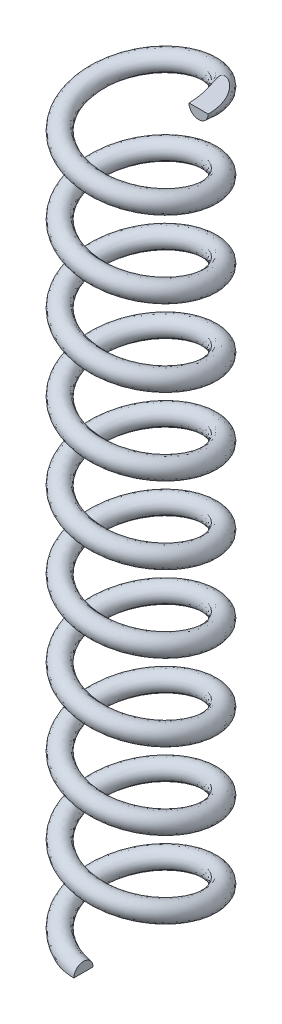
SolidWorks part; units mm, degrees
note: '?' marks a value the reader was unsure of.
ref_plane "Front Plane" through (0, 0, 0) normal (0, 0, 1) x (1, 0, 0)
ref_plane "Top Plane" through (0, 0, 0) normal (0, 1, 0) x (1, 0, 0)
ref_plane "Right Plane" through (0, 0, 0) normal (1, 0, 0) x (0, 0, -1)
sketch "Sketch1" plane through (0, 0, 0) normal (0, 1, 0) x (1, 0, 0)
  circle A0 centre (0, 0) radius 15
  dimension "D1" = 30
curve "Helix/Spiral1" pitch 20 height 195 turns 9.75
sketch "Sketch2" plane through (0, 0, 0) normal (1, 0, 0) x (0, 0, -1)
  circle A0 centre (-15, 0) radius 2.5
  spline S0 degree 3 poles (-15, 0) (-15, 0.3849) (-14.3278, 1.1617) (-11.4353, 2.3212) (-7.039, 3.4822) (-1.7171, 4.6428) (3.8306, 5.8036) (8.8746, 6.9643) (12.7515, 8.125) (14.9516, 9.2857) (15.1855, 10.4464) (13.4225, 11.6071) (9.8944, 12.7679) (5.0652, 13.9286) (-0.4301, 15.0893) (-5.8689, 16.25) (-10.5359, 17.4107) (-13.8174, 18.5714) (-15.2819, 19.7321) (-14.7367, 20.8929) (-12.2537, 22.0536) (-8.1593, 23.2143) (-2.9919, 24.375) (2.5689, 25.5357) (7.7919, 26.6964) (11.9903, 27.8571) (14.6119, 29.0179) (15.312, 30.1786) (13.9986, 31.3393) (10.8443, 32.5) (6.264, 33.6607) (0.8599, 34.8214) (-4.6572, 35.9821) (-9.5619, 37.1429) (-13.2092, 38.3036) (-15.1194, 39.4643) (-15.0414, 40.625) (-12.9855, 41.7857) (-9.2219, 42.9464) (-4.2456, 44.1071) (1.289, 45.2679) (6.6541, 46.4286) (11.1442, 47.5893) (14.1687, 48.75) (15.3301, 49.9107) (14.4755, 51.0714) (11.7174, 52.2321) (7.4184, 53.3929) (2.1438, 54.5536) (-3.4126, 55.7143) (-8.5203, 56.875) (-12.5075, 58.0357) (-14.85, 59.1964) (-15.2397, 60.3571) (-13.6253, 61.5179) (-10.2192, 62.6786) (-5.4692, 63.8393) (0, 65) (5.4692, 66.1607) (10.2192, 67.3214) (13.6253, 68.4821) (15.2397, 69.6429) (14.85, 70.8036) (12.5075, 71.9643) (8.5203, 73.125) (3.4126, 74.2857) (-2.1438, 75.4464) (-7.4184, 76.6071) (-11.7174, 77.7679) (-14.4755, 78.9286) (-15.3301, 80.0893) (-14.1687, 81.25) (-11.1442, 82.4107) (-6.6541, 83.5714) (-1.289, 84.7321) (4.2456, 85.8929) (9.2219, 87.0536) (12.9855, 88.2143) (15.0414, 89.375) (15.1194, 90.5357) (13.2092, 91.6964) (9.5619, 92.8571) (4.6572, 94.0179) (-0.8599, 95.1786) (-6.264, 96.3393) (-10.8443, 97.5) (-13.9986, 98.6607) (-15.312, 99.8214) (-14.6119, 100.9821) (-11.9903, 102.1429) (-7.7919, 103.3036) (-2.5689, 104.4643) (2.9919, 105.625) (8.1593, 106.7857) (12.2537, 107.9464) (14.7367, 109.1071) (15.2819, 110.2679) (13.8174, 111.4286) (10.5359, 112.5893) (5.8689, 113.75) (0.4301, 114.9107) (-5.0652, 116.0714) (-9.8944, 117.2321) (-13.4225, 118.3929) (-15.1855, 119.5536) (-14.9516, 120.7143) (-12.7515, 121.875) (-8.8746, 123.0357) (-3.8306, 124.1964) (1.7171, 125.3571) (7.039, 126.5179) (11.4353, 127.6786) (14.3278, 128.8393) (15.3361, 130) (14.3278, 131.1607) (11.4353, 132.3214) (7.039, 133.4821) (1.7171, 134.6429) (-3.8306, 135.8036) (-8.8746, 136.9643) (-12.7515, 138.125) (-14.9516, 139.2857) (-15.1855, 140.4464) (-13.4225, 141.6071) (-9.8944, 142.7679) (-5.0652, 143.9286) (0.4301, 145.0893) (5.8689, 146.25) (10.5359, 147.4107) (13.8174, 148.5714) (15.2819, 149.7321) (14.7367, 150.8929) (12.2537, 152.0536) (8.1593, 153.2143) (2.9919, 154.375) (-2.5689, 155.5357) (-7.7919, 156.6964) (-11.9903, 157.8571) (-14.6119, 159.0179) (-15.312, 160.1786) (-13.9986, 161.3393) (-10.8443, 162.5) (-6.264, 163.6607) (-0.8599, 164.8214) (4.6572, 165.9821) (9.5619, 167.1429) (13.2092, 168.3036) (15.1194, 169.4643) (15.0414, 170.625) (12.9855, 171.7857) (9.2219, 172.9464) (4.2456, 174.1071) (-1.289, 175.2679) (-6.6541, 176.4286) (-11.1442, 177.5893) (-14.1687, 178.75) (-15.3301, 179.9107) (-14.4755, 181.0714) (-11.7174, 182.2321) (-7.4184, 183.3929) (-2.1438, 184.5536) (3.4126, 185.7143) (8.5203, 186.875) (12.5075, 188.0357) (14.85, 189.1964) (15.2396, 190.3572) (13.6256, 191.5178) (10.218, 192.6788) (5.4736, 193.8383) (1.8136, 194.6151) (0, 195) knots 0 0 0 0 0.005952 0.011905 0.017857 0.02381 0.029762 0.035714 0.041667 0.047619 0.053571 0.059524 0.065476 0.071429 0.077381 0.083333 0.089286 0.095238 0.10119 0.107143 0.113095 0.119048 0.125 0.130952 0.136905 0.142857 0.14881 0.154762 0.160714 0.166667 0.172619 0.178571 0.184524 0.190476 0.196429 0.202381 0.208333 0.214286 0.220238 0.22619 0.232143 0.238095 0.244048 0.25 0.255952 0.261905 0.267857 0.27381 0.279762 0.285714 0.291667 0.297619 0.303571 0.309524 0.315476 0.321429 0.327381 0.333333 0.339286 0.345238 0.35119 0.357143 0.363095 0.369048 0.375 0.380952 0.386905 0.392857 0.39881 0.404762 0.410714 0.416667 0.422619 0.428571 0.434524 0.440476 0.446429 0.452381 0.458333 0.464286 0.470238 0.47619 0.482143 0.488095 0.494048 0.5 0.505952 0.511905 0.517857 0.52381 0.529762 0.535714 0.541667 0.547619 0.553571 0.559524 0.565476 0.571429 0.577381 0.583333 0.589286 0.595238 0.60119 0.607143 0.613095 0.619048 0.625 0.630952 0.636905 0.642857 0.64881 0.654762 0.660714 0.666667 0.672619 0.678571 0.684524 0.690476 0.696429 0.702381 0.708333 0.714286 0.720238 0.72619 0.732143 0.738095 0.744048 0.75 0.755952 0.761905 0.767857 0.77381 0.779762 0.785714 0.791667 0.797619 0.803571 0.809524 0.815476 0.821429 0.827381 0.833333 0.839286 0.845238 0.85119 0.857143 0.863095 0.869048 0.875 0.880952 0.886905 0.892857 0.89881 0.904762 0.910714 0.916667 0.922619 0.928571 0.934524 0.940476 0.946429 0.952381 0.958333 0.964286 0.970238 0.97619 0.982143 0.988095 0.994048 1 1 1 1 construction
  dimension "D1" = 5
sweep "Sweep1" add profiles "Sketch2" path "Helix/Spiral1"
ref_axis "Axis1" through (0, 210.25, 0) along (0, -1, 0)?
sketch "Sketch3" plane through (0, 0, 0) normal (0, 0, 1) x (1, 0, 0)
  line L0 (0, -2.5) -> (0, 2.5) construction
  line L1 (-100.2397, 242.6252) -> (158.3015, 242.6252)
  line L2 (-100.2397, 242.6252) -> (-100.2397, 195)
  line L3 (-100.2397, 195) -> (158.3015, 195)
  line L4 (158.3015, 242.6252) -> (158.3015, 195)
  line L5 (37.8113, 0) -> (-77.0645, 0)
  line L6 (37.8113, 0) -> (37.8113, -35.3641)
  line L7 (37.8113, -35.3641) -> (-77.0645, -35.3641)
  line L8 (-77.0645, 0) -> (-77.0645, -35.3641)
  line L9 (0, -2.5) -> (0, 2.5) construction
  circle A0 centre (15, 195) radius 2.5 construction
  circle A1 centre (15, 195) radius 2.5 construction
extrude "Cut-Extrude1" cut sketch "Sketch3" against normal through all and the other way through all
